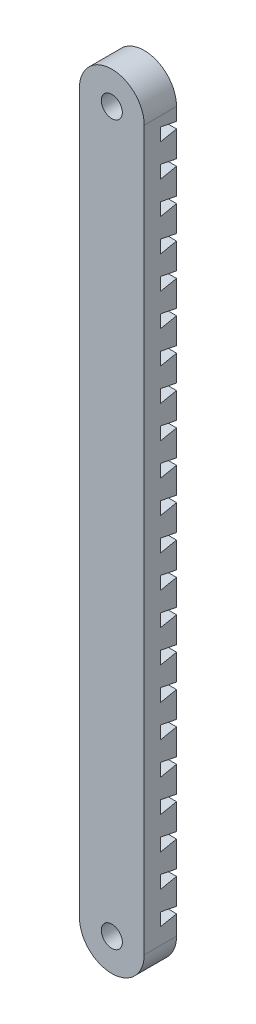
SolidWorks part; units mm, degrees
ref_plane "Front Plane" through (0, 0, 0) normal (0, 0, 1) x (1, 0, 0)
ref_plane "Top Plane" through (0, 0, 0) normal (0, 1, 0) x (1, 0, 0)
ref_plane "Right Plane" through (0, 0, 0) normal (1, 0, 0) x (0, 0, -1)
sketch "Sketch1" plane through (0, 0, 0) normal (0, 0, 1) x (1, 0, 0)
  line L0 (111, 0) -> (-111, 0) construction
  line L3 (0, 111) -> (0, -111) construction
  line L4 (0, 0) -> (0, -111) construction
  line L5 (5, 0) -> (5, -111)
  line L6 (-5, 0) -> (-5, -111)
  circle A2 centre (0, 0) radius 1.625
  circle A3 centre (0, -111) radius 1.625
  arc A4 (5, 0) -> (-5, 0) centre (0, 0) ccw
  arc A5 (-5, -111) -> (5, -111) centre (0, -111) ccw
  point P0 (0, -55.5)
  dimension "D1" = 5
  dimension "D2" = 111
  dimension "D3" = 3.25
  dimension "D4" = 3.25
extrude "Boss-Extrude1" add sketch "Sketch1" along normal blind 5
sketch "Sketch2" plane through (5, 0, 0) normal (1, 0, 0) x (0, 0, -1)
  line L0 (0, -2) -> (0, -3)
  line L5 (0, -2) -> (-2.5, -1.5)
  line L6 (-2.5, -1.5) -> (-2.5, -3.5)
  line L143 (0, -111) -> (0, 0) construction
  line L148 (-5, 0) -> (0, 0) construction
  line L285 (-2.5, -3.5) -> (0, -3)
  line L286 (0, -2.5) -> (-2.5, -2.5) construction
  line L287 (0, -7) -> (0, -8)
  line L288 (-2.5, -8.5) -> (0, -8)
  line L289 (-2.5, -6.5) -> (-2.5, -8.5)
  line L290 (0, -7) -> (-2.5, -6.5)
  line L291 (0, -12) -> (0, -13)
  line L292 (-2.5, -13.5) -> (0, -13)
  line L293 (-2.5, -11.5) -> (-2.5, -13.5)
  line L294 (0, -12) -> (-2.5, -11.5)
  line L295 (0, -17) -> (0, -18)
  line L296 (-2.5, -18.5) -> (0, -18)
  line L297 (-2.5, -16.5) -> (-2.5, -18.5)
  line L298 (0, -17) -> (-2.5, -16.5)
  line L299 (0, -22) -> (0, -23)
  line L300 (-2.5, -23.5) -> (0, -23)
  line L301 (-2.5, -21.5) -> (-2.5, -23.5)
  line L302 (0, -22) -> (-2.5, -21.5)
  line L303 (0, -27) -> (0, -28)
  line L304 (-2.5, -28.5) -> (0, -28)
  line L305 (-2.5, -26.5) -> (-2.5, -28.5)
  line L306 (0, -27) -> (-2.5, -26.5)
  line L307 (0, -32) -> (0, -33)
  line L308 (-2.5, -33.5) -> (0, -33)
  line L309 (-2.5, -31.5) -> (-2.5, -33.5)
  line L310 (0, -32) -> (-2.5, -31.5)
  line L311 (0, -37) -> (0, -38)
  line L312 (-2.5, -38.5) -> (0, -38)
  line L313 (-2.5, -36.5) -> (-2.5, -38.5)
  line L314 (0, -37) -> (-2.5, -36.5)
  line L315 (0, -42) -> (0, -43)
  line L316 (-2.5, -43.5) -> (0, -43)
  line L317 (-2.5, -41.5) -> (-2.5, -43.5)
  line L318 (0, -42) -> (-2.5, -41.5)
  line L319 (0, -47) -> (0, -48)
  line L320 (-2.5, -48.5) -> (0, -48)
  line L321 (-2.5, -46.5) -> (-2.5, -48.5)
  line L322 (0, -47) -> (-2.5, -46.5)
  line L323 (0, -52) -> (0, -53)
  line L324 (-2.5, -53.5) -> (0, -53)
  line L325 (-2.5, -51.5) -> (-2.5, -53.5)
  line L326 (0, -52) -> (-2.5, -51.5)
  line L327 (0, -57) -> (0, -58)
  line L328 (-2.5, -58.5) -> (0, -58)
  line L329 (-2.5, -56.5) -> (-2.5, -58.5)
  line L330 (0, -57) -> (-2.5, -56.5)
  line L331 (0, -62) -> (0, -63)
  line L332 (-2.5, -63.5) -> (0, -63)
  line L333 (-2.5, -61.5) -> (-2.5, -63.5)
  line L334 (0, -62) -> (-2.5, -61.5)
  line L335 (0, -67) -> (0, -68)
  line L336 (-2.5, -68.5) -> (0, -68)
  line L337 (-2.5, -66.5) -> (-2.5, -68.5)
  line L338 (0, -67) -> (-2.5, -66.5)
  line L339 (0, -72) -> (0, -73)
  line L340 (-2.5, -73.5) -> (0, -73)
  line L341 (-2.5, -71.5) -> (-2.5, -73.5)
  line L342 (0, -72) -> (-2.5, -71.5)
  line L343 (0, -77) -> (0, -78)
  line L344 (-2.5, -78.5) -> (0, -78)
  line L345 (-2.5, -76.5) -> (-2.5, -78.5)
  line L346 (0, -77) -> (-2.5, -76.5)
  line L347 (0, -82) -> (0, -83)
  line L348 (-2.5, -83.5) -> (0, -83)
  line L349 (-2.5, -81.5) -> (-2.5, -83.5)
  line L350 (0, -82) -> (-2.5, -81.5)
  line L351 (0, -87) -> (0, -88)
  line L352 (-2.5, -88.5) -> (0, -88)
  line L353 (-2.5, -86.5) -> (-2.5, -88.5)
  line L354 (0, -87) -> (-2.5, -86.5)
  line L355 (0, -92) -> (0, -93)
  line L356 (-2.5, -93.5) -> (0, -93)
  line L357 (-2.5, -91.5) -> (-2.5, -93.5)
  line L358 (0, -92) -> (-2.5, -91.5)
  line L359 (0, -97) -> (0, -98)
  line L360 (-2.5, -98.5) -> (0, -98)
  line L361 (-2.5, -96.5) -> (-2.5, -98.5)
  line L362 (0, -97) -> (-2.5, -96.5)
  line L363 (0, -102) -> (0, -103)
  line L364 (-2.5, -103.5) -> (0, -103)
  line L365 (-2.5, -101.5) -> (-2.5, -103.5)
  line L366 (0, -102) -> (-2.5, -101.5)
  line L367 (0, -107) -> (0, -108)
  line L368 (-2.5, -108.5) -> (0, -108)
  line L369 (-2.5, -106.5) -> (-2.5, -108.5)
  line L370 (0, -107) -> (-2.5, -106.5)
  dimension "D1" = 1
  dimension "D2" = 1
  dimension "D3" = 1
  dimension "D5" = 2.5
  dimension "D4" = 2.5
  dimension "D6" = 2.5
  dimension "D7" = 22
extrude "Cut-Extrude1" cut sketch "Sketch2" against normal through all
